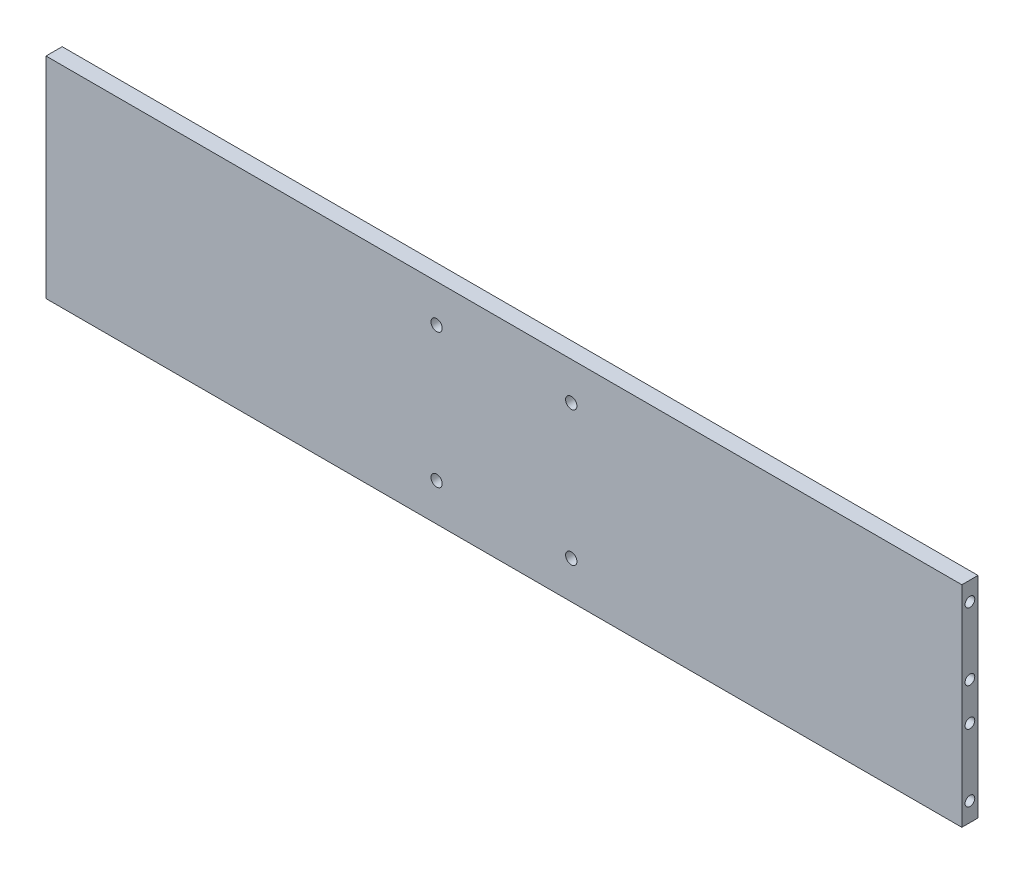
SolidWorks part; units mm, degrees
ref_plane "Front Plane" through (0, 0, 0) normal (0, 0, 1) x (1, 0, 0)
ref_plane "Top Plane" through (0, 0, 0) normal (0, 1, 0) x (1, 0, 0)
ref_plane "Right Plane" through (0, 0, 0) normal (1, 0, 0) x (0, 0, -1)
sketch "Sketch1" plane through (0, 0, 0) normal (0, 0, 1) x (1, 0, 0)
  line L1 (-170, -39) -> (170, -39)
  line L2 (-170, -39) -> (-170, 39)
  line L3 (-170, 39) -> (170, 39)
  line L4 (170, -39) -> (170, 39)
  line L5 (-170, -39) -> (170, 39) construction
  line L6 (-170, 39) -> (170, -39) construction
  line L7 (-25, -25) -> (25, -25) construction
  line L8 (-25, -25) -> (-25, 25) construction
  line L9 (-25, 25) -> (25, 25) construction
  line L10 (25, -25) -> (25, 25) construction
  line L11 (-25, -25) -> (25, 25) construction
  line L12 (-25, 25) -> (25, -25) construction
  circle A0 centre (-25, 25) radius 2.1
  circle A1 centre (25, 25) radius 2.1
  circle A2 centre (25, -25) radius 2.1
  circle A3 centre (-25, -25) radius 2.1
  point P0 (0, 0)
  point P6 (0, 0)
  dimension "D1" = 340
  dimension "D2" = 78
  dimension "D3" = 50
  dimension "D4" = 50
extrude "Boss-Extrude1" add sketch "Sketch1" along normal blind 6
sketch "Sketch2" plane through (170, 0, 0) normal (1, 0, 0) x (0, 0, -1)
  line L0 (-6, 0) -> (0, 0) construction
  line L1 (-6, -39) -> (-6, 39) construction
  line L2 (0, -39) -> (0, 39) construction
  line L3 (-3, 39) -> (-3, 0) construction
  line L4 (-6, 39) -> (0, 39) construction
  circle A0 centre (-3, 32) radius 1.8
  circle A1 centre (-3, 7) radius 1.8
  circle A2 centre (-3, -7) radius 1.8
  circle A3 centre (-3, -32) radius 1.8
  point P14 (-3, 19.5)
  dimension "D1" = 25
  dimension "D2" = 12.5
extrude "Cut-Extrude1" cut sketch "Sketch2" against normal up to next
